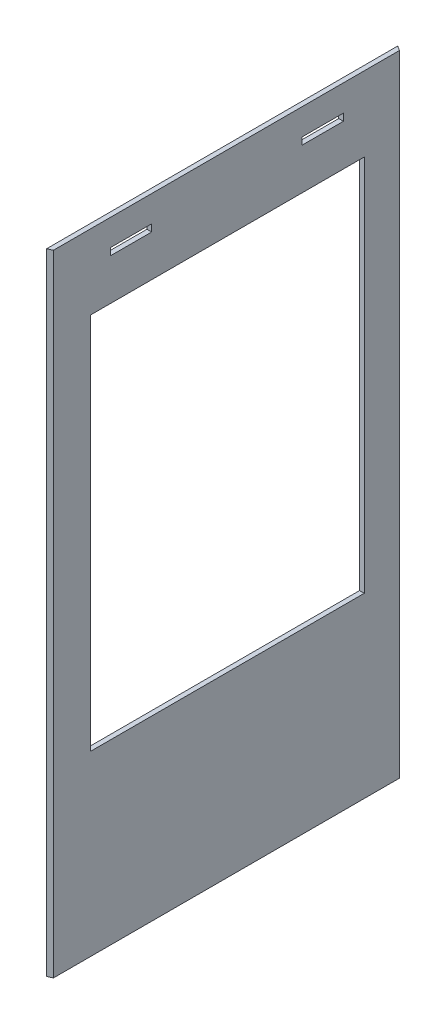
SolidWorks part; units mm, degrees
ref_plane "Спереди" through (0, 0, 0) normal (0, 0, 1) x (1, 0, 0)
ref_plane "Сверху" through (0, 0, 0) normal (0, 1, 0) x (1, 0, 0)
ref_plane "Справа" through (0, 0, 0) normal (1, 0, 0) x (0, 0, -1)
sketch "Эскиз1" plane through (0, 0, 0) normal (0, 1, 0) x (1, 0, 0)
  line L0 (4.0186, 1.7475) -> (79.181, -66.868) construction
  line L1 (0, 0) -> (4, 1.7645)
  line L2 (0, 0) -> (0, 297.3876)
  line L3 (0, 297.3876) -> (4, 294.8273)
  line L4 (4, 1.7645) -> (4, 294.8273)
  dimension "D1" = 4
extrude "Вытянуть1" add sketch "Эскиз1" along normal up to surface (533.7137 mm away)
sketch "Эскиз2" plane through (0, 0, 0) normal (-1, 0, 0) x (0, 0, 1)
  line L0 (-272.3275, 260.902) -> (-272.3275, -22.3628)
  line L1 (-272.3275, 260.902) -> (-25.1909, 260.902)
  line L3 (-272.3275, -22.3628) -> (-25.1909, -22.3628)
  line L4 (-25.1909, 260.902) -> (-25.1909, -22.3628)
  line L6 (-264.3275, 152.3571) -> (-192.5685, 152.3571) construction
sketch "Sketch1" plane through (0, 0, 0) normal (-1, 0, 0) x (0, 0, 1)
  line L0 (-149.0559, 533.7137) -> (-149.0559, 365.9424) construction
  line L2 (-466.2387, 150.5) -> (190.429, 150.5) construction
  line L3 (-297.6324, 0.5) -> (0.0403, 0.5) construction
  line L4 (-507.1548, 470.5) -> (192.6943, 470.5) construction
  line L5 (-451.9035, 310.5) -> (226.1799, 310.5) construction
  line L7 (-33.0559, 150.5) -> (-265.0559, 150.5)
  line L8 (-33.0559, 150.5) -> (-33.0559, 470.5)
  line L9 (-33.0559, 470.5) -> (-265.0559, 470.5)
  line L10 (-265.0559, 150.5) -> (-265.0559, 470.5)
  line L11 (-33.0559, 150.5) -> (-265.0559, 470.5) construction
  line L12 (-33.0559, 470.5) -> (-265.0559, 150.5) construction
  point P9 (-149.0559, 310.5)
  dimension "D1" = 150
  dimension "D2" = 320
  dimension "D3" = 160
extrude "Cut-Extrude1" cut sketch "Sketch1" against normal through all
sketch "Sketch2" plane through (0, 0, 0) normal (-1, 0, 0) x (0, 0, 1)
  line L0 (-325.7416, 505.5) -> (32.5763, 505.5) construction
  line L1 (-33.0559, 470.5) -> (-265.0559, 470.5) construction
  line L2 (-247.3876, 583.7888) -> (-247.3876, 553.0639) construction
  line L4 (-297.3876, 533.7137) -> (-297.3876, 0) construction
  line L5 (-148.6938, 533.7137) -> (-148.6938, 623.8727) construction
  line L6 (-247.3876, 505.5) -> (-212.3876, 505.5)
  line L7 (-247.3876, 505.5) -> (-247.3876, 511.5)
  line L8 (-247.3876, 511.5) -> (-212.3876, 511.5)
  line L9 (-212.3876, 505.5) -> (-212.3876, 511.5)
  line L11 (-50, 505.5) -> (-50, 511.5)
  line L12 (-50, 505.5) -> (-85, 505.5)
  line L13 (-85, 505.5) -> (-85, 511.5)
  line L14 (-50, 511.5) -> (-85, 511.5)
  dimension "D1" = 35
  dimension "D2" = 50
extrude "Cut-Extrude2" cut sketch "Sketch2" against normal through all
